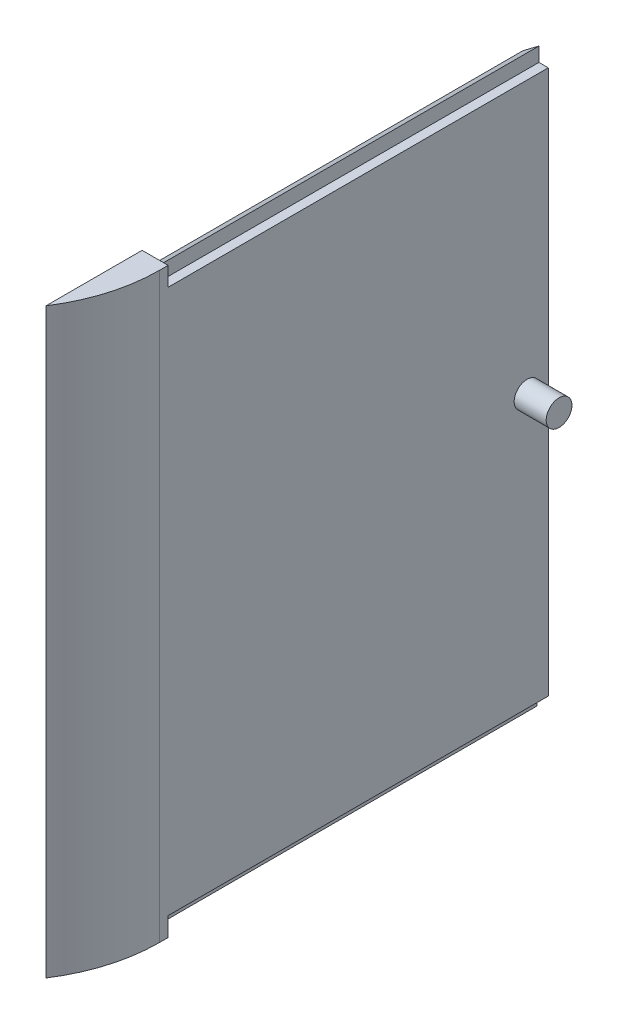
SolidWorks part; units mm, degrees
ref_plane "Front Plane" through (0, 0, 0) normal (0, 0, 1) x (1, 0, 0)
ref_plane "Top Plane" through (0, 0, 0) normal (0, 1, 0) x (1, 0, 0)
ref_plane "Right Plane" through (0, 0, 0) normal (1, 0, 0) x (0, 0, -1)
sketch "Sketch1" plane through (0, 0, 0) normal (0, 0, 1) x (1, 0, 0)
  line L0 (33.6841, -148) -> (37.1841, -148) construction
  line L8 (37.1841, -148) -> (40, -148)
  line L9 (37.1841, -151.55) -> (37.1841, -148)
  line L11 (33.6841, -148) -> (37.1841, -151.55)
  line L12 (37.6679, -12) -> (40, -12)
  line L14 (33.6841, -11.4469) -> (37.6679, -8.45)
  line L15 (37.6679, -8.45) -> (37.6679, -12)
  line L16 (40, -12) -> (40, -148)
  line L18 (33.6841, -11.4469) -> (33.6841, -148)
  dimension "D1" = 3.55
  dimension "D2" = 3.5
extrude "Boss-Extrude1" add sketch "Sketch1" against normal up to surface (95.0113 mm away)
sketch "Sketch4" plane through (0, 0, 0) normal (0, 0, 1) x (1, 0, 0)
  line L1 (40, -152.75) -> (33.5, -152.75)
  line L3 (40, -7.25) -> (33.5, -7.25)
  line L4 (33.5, -152.75) -> (33.5, -7.25)
  line L5 (40, -80) -> (33.5, -80) construction
  line L6 (40, -7.25) -> (40, -80)
  line L7 (40, -80) -> (40, -152.75)
  point P9 (0, 0)
  point P10 (0, 0)
  dimension "D1" = 145.5
  dimension "D2" = 6.5
extrude "Boss-Extrude2" add sketch "Sketch4" along normal blind 24
fillet "Fillet1" radius 40 1 edges at (40, -80, 24)
sketch "Sketch5" plane through (40, 0, 0) normal (1, 0, 0) x (0, 0, -1)
  line L0 (89.7148, -12) -> (89.7148, -148) construction
  line L1 (95.0113, -12) -> (0, -12) construction
  line L2 (95.0113, -148) -> (0, -148) construction
  circle A0 centre (89.7148, -80) radius 3.2191
extrude "Boss-Extrude3" add sketch "Sketch5" along normal blind 8
